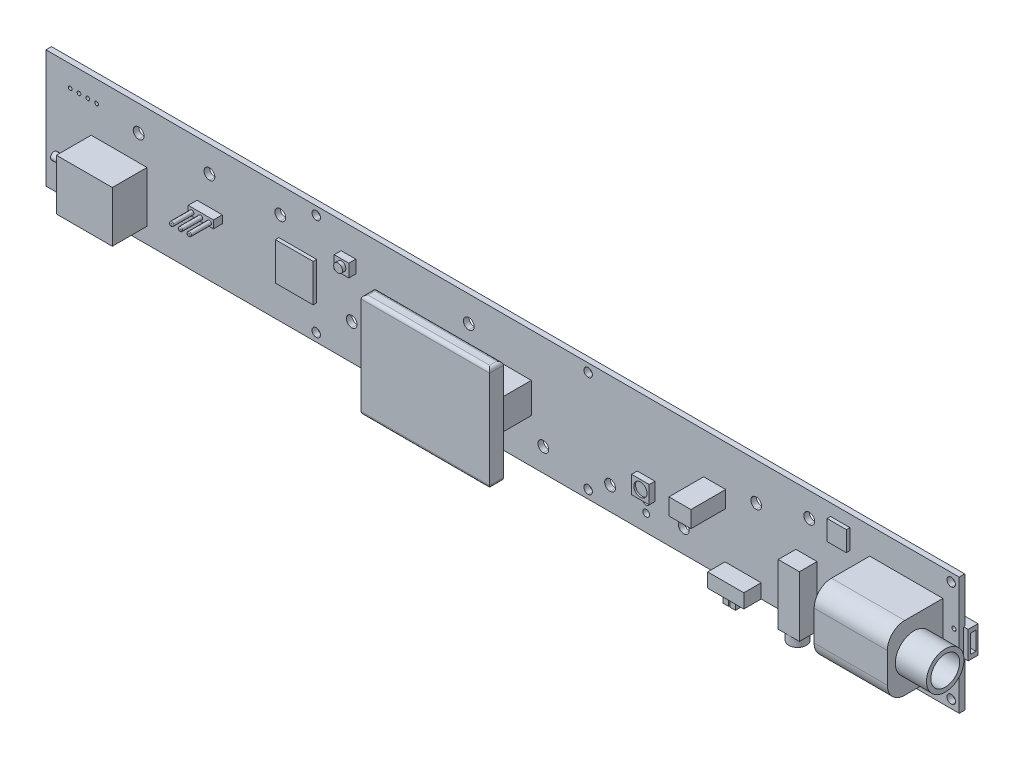
SolidWorks part; units mm, degrees
ref_plane "Front Plane" through (0, 0, 0) normal (0, 0, 1) x (1, 0, 0)
ref_plane "Top Plane" through (0, 0, 0) normal (0, 1, 0) x (1, 0, 0)
ref_plane "Right Plane" through (0, 0, 0) normal (1, 0, 0) x (0, 0, -1)
sketch "Model" plane through (0, 0, 0) normal (0, 0, 1) x (1, 0, 0)
  line L0 (34.6044, 5.9762) -> (297.6294, 5.9762)
  line L1 (297.6294, 5.9762) -> (297.6294, 39.9762)
  line L2 (297.6294, 39.9762) -> (34.6044, 39.9762)
  line L3 (34.6044, 39.9762) -> (34.6044, 5.9762)
  spline S24 degree 3 poles (262.1971, 34.516) (262.0217, 34.516) (261.8796, 34.6582) (261.8796, 34.8335) (261.8796, 35.0089) (262.0217, 35.151) (262.1971, 35.151) knots 2 2 2 2 3 3 3 4 4 4 4
  spline S25 degree 3 poles (262.1971, 35.151) (262.3725, 35.151) (262.5146, 35.0089) (262.5146, 34.8335) (262.5146, 34.6582) (262.3725, 34.516) (262.1971, 34.516) knots 0 0 0 0 1 1 1 2 2 2 2
  spline S48 degree 3 poles (264.4116, 33.4087) (264.2363, 33.4087) (264.0941, 33.5509) (264.0941, 33.7262) (264.0941, 33.9016) (264.2363, 34.0437) (264.4116, 34.0437) knots 2 2 2 2 3 3 3 4 4 4 4
  spline S49 degree 3 poles (264.4116, 34.0437) (264.587, 34.0437) (264.7291, 33.9016) (264.7291, 33.7262) (264.7291, 33.5509) (264.587, 33.4087) (264.4116, 33.4087) knots 0 0 0 0 1 1 1 2 2 2 2
  spline S60 degree 3 poles (295.3194, 36.3663) (294.6456, 36.3663) (294.0994, 36.9125) (294.0994, 37.5863) (294.0994, 38.26) (294.6456, 38.8062) (295.3194, 38.8062) knots 2 2 2 2 3 3 3 4 4 4 4
  spline S61 degree 3 poles (295.3194, 38.8062) (295.9931, 38.8062) (296.5394, 38.26) (296.5394, 37.5863) (296.5394, 36.9125) (295.9931, 36.3663) (295.3194, 36.3663) knots 0 0 0 0 1 1 1 2 2 2 2
  spline S100 degree 3 poles (264.4116, 32.3015) (264.2363, 32.3015) (264.0941, 32.4436) (264.0941, 32.619) (264.0941, 32.7943) (264.2363, 32.9365) (264.4116, 32.9365) knots 2 2 2 2 3 3 3 4 4 4 4
  spline S101 degree 3 poles (264.4116, 32.9365) (264.587, 32.9365) (264.7291, 32.7943) (264.7291, 32.619) (264.7291, 32.4436) (264.587, 32.3015) (264.4116, 32.3015) knots 0 0 0 0 1 1 1 2 2 2 2
  spline S118 degree 3 poles (262.1971, 33.4087) (262.0217, 33.4087) (261.8796, 33.5509) (261.8796, 33.7262) (261.8796, 33.9016) (262.0217, 34.0437) (262.1971, 34.0437) knots 2 2 2 2 3 3 3 4 4 4 4
  spline S119 degree 3 poles (262.1971, 34.0437) (262.3725, 34.0437) (262.5146, 33.9016) (262.5146, 33.7262) (262.5146, 33.5509) (262.3725, 33.4087) (262.1971, 33.4087) knots 0 0 0 0 1 1 1 2 2 2 2
  spline S128 degree 3 poles (112.4394, 36.3763) (111.7656, 36.3763) (111.2194, 36.9225) (111.2194, 37.5962) (111.2194, 38.27) (111.7656, 38.8162) (112.4394, 38.8162) knots 2 2 2 2 3 3 3 4 4 4 4
  spline S129 degree 3 poles (112.4394, 38.8162) (113.1132, 38.8162) (113.6594, 38.27) (113.6594, 37.5962) (113.6594, 36.9225) (113.1132, 36.3763) (112.4394, 36.3763) knots 0 0 0 0 1 1 1 2 2 2 2
  spline S146 degree 3 poles (190.7594, 7.1563) (190.0856, 7.1563) (189.5394, 7.7025) (189.5394, 8.3763) (189.5394, 9.05) (190.0856, 9.5962) (190.7594, 9.5962) knots 2 2 2 2 3 3 3 4 4 4 4
  spline S147 degree 3 poles (190.7594, 9.5962) (191.4331, 9.5962) (191.9794, 9.05) (191.9794, 8.3763) (191.9794, 7.7025) (191.4331, 7.1563) (190.7594, 7.1563) knots 0 0 0 0 1 1 1 2 2 2 2
  spline S150 degree 3 poles (190.7594, 36.3663) (190.0856, 36.3663) (189.5394, 36.9125) (189.5394, 37.5863) (189.5394, 38.26) (190.0856, 38.8062) (190.7594, 38.8062) knots 2 2 2 2 3 3 3 4 4 4 4
  spline S151 degree 3 poles (190.7594, 38.8062) (191.4331, 38.8062) (191.9794, 38.26) (191.9794, 37.5863) (191.9794, 36.9125) (191.4331, 36.3663) (190.7594, 36.3663) knots 0 0 0 0 1 1 1 2 2 2 2
  spline S154 degree 3 poles (263.3044, 33.4087) (263.129, 33.4087) (262.9869, 33.5509) (262.9869, 33.7262) (262.9869, 33.9016) (263.129, 34.0437) (263.3044, 34.0437) knots 2 2 2 2 3 3 3 4 4 4 4
  spline S155 degree 3 poles (263.3044, 34.0437) (263.4797, 34.0437) (263.6219, 33.9016) (263.6219, 33.7262) (263.6219, 33.5509) (263.4797, 33.4087) (263.3044, 33.4087) knots 0 0 0 0 1 1 1 2 2 2 2
  spline S156 degree 3 poles (263.3044, 34.516) (263.129, 34.516) (262.9869, 34.6582) (262.9869, 34.8335) (262.9869, 35.0089) (263.129, 35.151) (263.3044, 35.151) knots 2 2 2 2 3 3 3 4 4 4 4
  spline S157 degree 3 poles (263.3044, 35.151) (263.4797, 35.151) (263.6219, 35.0089) (263.6219, 34.8335) (263.6219, 34.6582) (263.4797, 34.516) (263.3044, 34.516) knots 0 0 0 0 1 1 1 2 2 2 2
  spline S220 degree 3 poles (262.1971, 32.3015) (262.0217, 32.3015) (261.8796, 32.4436) (261.8796, 32.619) (261.8796, 32.7943) (262.0217, 32.9365) (262.1971, 32.9365) knots 2 2 2 2 3 3 3 4 4 4 4
  spline S221 degree 3 poles (262.1971, 32.9365) (262.3725, 32.9365) (262.5146, 32.7943) (262.5146, 32.619) (262.5146, 32.4436) (262.3725, 32.3015) (262.1971, 32.3015) knots 0 0 0 0 1 1 1 2 2 2 2
  spline S222 degree 3 poles (263.3044, 32.3015) (263.129, 32.3015) (262.9869, 32.4436) (262.9869, 32.619) (262.9869, 32.7943) (263.129, 32.9365) (263.3044, 32.9365) knots 2 2 2 2 3 3 3 4 4 4 4
  spline S223 degree 3 poles (263.3044, 32.9365) (263.4797, 32.9365) (263.6219, 32.7943) (263.6219, 32.619) (263.6219, 32.4436) (263.4797, 32.3015) (263.3044, 32.3015) knots 0 0 0 0 1 1 1 2 2 2 2
  spline S228 degree 3 poles (264.4116, 34.516) (264.2363, 34.516) (264.0941, 34.6582) (264.0941, 34.8335) (264.0941, 35.0089) (264.2363, 35.151) (264.4116, 35.151) knots 2 2 2 2 3 3 3 4 4 4 4
  spline S229 degree 3 poles (264.4116, 35.151) (264.587, 35.151) (264.7291, 35.0089) (264.7291, 34.8335) (264.7291, 34.6582) (264.587, 34.516) (264.4116, 34.516) knots 0 0 0 0 1 1 1 2 2 2 2
  spline S252 degree 3 poles (295.3194, 7.1563) (294.6456, 7.1563) (294.0994, 7.7025) (294.0994, 8.3763) (294.0994, 9.05) (294.6456, 9.5962) (295.3194, 9.5962) knots 2 2 2 2 3 3 3 4 4 4 4
  spline S253 degree 3 poles (295.3194, 9.5962) (295.9931, 9.5962) (296.5394, 9.05) (296.5394, 8.3763) (296.5394, 7.7025) (295.9931, 7.1563) (295.3194, 7.1563) knots 0 0 0 0 1 1 1 2 2 2 2
  spline S286 degree 3 poles (112.4394, 7.1563) (111.7656, 7.1563) (111.2194, 7.7025) (111.2194, 8.3763) (111.2194, 9.05) (111.7656, 9.5962) (112.4394, 9.5962) knots 2 2 2 2 3 3 3 4 4 4 4
  spline S287 degree 3 poles (112.4394, 9.5962) (113.1132, 9.5962) (113.6594, 9.05) (113.6594, 8.3763) (113.6594, 7.7025) (113.1132, 7.1563) (112.4394, 7.1563) knots 0 0 0 0 1 1 1 2 2 2 2
  spline S300 degree 3 poles (197.0694, 11.0863) (196.2133, 11.0863) (195.5194, 11.7802) (195.5194, 12.6363) (195.5194, 13.4923) (196.2133, 14.1862) (197.0694, 14.1862) knots 2 2 2 2 3 3 3 4 4 4 4
  spline S301 degree 3 poles (197.0694, 14.1862) (197.9254, 14.1862) (198.6194, 13.4923) (198.6194, 12.6363) (198.6194, 11.7802) (197.9254, 11.0863) (197.0694, 11.0863) knots 0 0 0 0 1 1 1 2 2 2 2
  spline S306 degree 3 poles (122.6494, 14.6662) (121.7933, 14.6662) (121.0994, 15.3602) (121.0994, 16.2162) (121.0994, 17.0723) (121.7933, 17.7662) (122.6494, 17.7662) knots 2 2 2 2 3 3 3 4 4 4 4
  spline S307 degree 3 poles (122.6494, 17.7662) (123.5054, 17.7662) (124.1994, 17.0723) (124.1994, 16.2162) (124.1994, 15.3602) (123.5054, 14.6662) (122.6494, 14.6662) knots 0 0 0 0 1 1 1 2 2 2 2
  spline S312 degree 3 poles (81.6794, 30.9962) (80.8233, 30.9962) (80.1294, 31.6902) (80.1294, 32.5462) (80.1294, 33.4023) (80.8233, 34.0962) (81.6794, 34.0962) knots 2 2 2 2 3 3 3 4 4 4 4
  spline S313 degree 3 poles (81.6794, 34.0962) (82.5354, 34.0962) (83.2294, 33.4023) (83.2294, 32.5462) (83.2294, 31.6902) (82.5354, 30.9962) (81.6794, 30.9962) knots 0 0 0 0 1 1 1 2 2 2 2
  spline S314 degree 3 poles (156.3794, 30.9962) (155.5233, 30.9962) (154.8294, 31.6902) (154.8294, 32.5462) (154.8294, 33.4023) (155.5233, 34.0962) (156.3794, 34.0962) knots 2 2 2 2 3 3 3 4 4 4 4
  spline S315 degree 3 poles (156.3794, 34.0962) (157.2354, 34.0962) (157.9294, 33.4023) (157.9294, 32.5462) (157.9294, 31.6902) (157.2354, 30.9962) (156.3794, 30.9962) knots 0 0 0 0 1 1 1 2 2 2 2
  spline S316 degree 3 poles (254.4194, 31.4562) (253.5633, 31.4562) (252.8694, 32.1502) (252.8694, 33.0062) (252.8694, 33.8623) (253.5633, 34.5562) (254.4194, 34.5562) knots 2 2 2 2 3 3 3 4 4 4 4
  spline S317 degree 3 poles (254.4194, 34.5562) (255.2754, 34.5562) (255.9694, 33.8623) (255.9694, 33.0062) (255.9694, 32.1502) (255.2754, 31.4562) (254.4194, 31.4562) knots 0 0 0 0 1 1 1 2 2 2 2
  spline S318 degree 3 poles (137.8394, 11.0863) (136.9833, 11.0863) (136.2894, 11.7802) (136.2894, 12.6363) (136.2894, 13.4923) (136.9833, 14.1862) (137.8394, 14.1862) knots 2 2 2 2 3 3 3 4 4 4 4
  spline S319 degree 3 poles (137.8394, 14.1862) (138.6954, 14.1862) (139.3894, 13.4923) (139.3894, 12.6363) (139.3894, 11.7802) (138.6954, 11.0863) (137.8394, 11.0863) knots 0 0 0 0 1 1 1 2 2 2 2
  spline S320 degree 3 poles (253.6294, 8.814) (253.1876, 8.814) (252.8294, 9.1722) (252.8294, 9.614) (252.8294, 10.0558) (253.1876, 10.414) (253.6294, 10.414) knots 2 2 2 2 3 3 3 4 4 4 4
  spline S321 degree 3 poles (253.6294, 10.414) (254.0712, 10.414) (254.4294, 10.0558) (254.4294, 9.614) (254.4294, 9.1722) (254.0712, 8.814) (253.6294, 8.814) knots 0 0 0 0 1 1 1 2 2 2 2
  spline S322 degree 3 poles (253.6294, 15.814) (253.1876, 15.814) (252.8294, 16.1722) (252.8294, 16.614) (252.8294, 17.0558) (253.1876, 17.414) (253.6294, 17.414) knots 2 2 2 2 3 3 3 4 4 4 4
  spline S323 degree 3 poles (253.6294, 17.414) (254.0712, 17.414) (254.4294, 17.0558) (254.4294, 16.614) (254.4294, 16.1722) (254.0712, 15.814) (253.6294, 15.814) knots 0 0 0 0 1 1 1 2 2 2 2
  spline S324 degree 3 poles (218.2994, 11.0863) (217.4433, 11.0863) (216.7494, 11.7802) (216.7494, 12.6363) (216.7494, 13.4923) (217.4433, 14.1862) (218.2994, 14.1862) knots 2 2 2 2 3 3 3 4 4 4 4
  spline S325 degree 3 poles (218.2994, 14.1862) (219.1554, 14.1862) (219.8494, 13.4923) (219.8494, 12.6363) (219.8494, 11.7802) (219.1554, 11.0863) (218.2994, 11.0863) knots 0 0 0 0 1 1 1 2 2 2 2
  spline S326 degree 3 poles (237.3794, 7.5013) (237.1032, 7.5013) (236.8794, 7.7251) (236.8794, 8.0013) (236.8794, 8.2774) (237.1032, 8.5013) (237.3794, 8.5013) knots 2 2 2 2 3 3 3 4 4 4 4
  spline S327 degree 3 poles (237.3794, 8.5013) (237.6555, 8.5013) (237.8794, 8.2774) (237.8794, 8.0013) (237.8794, 7.7251) (237.6555, 7.5013) (237.3794, 7.5013) knots 0 0 0 0 1 1 1 2 2 2 2
  spline S328 degree 3 poles (235.3794, 7.5013) (235.1032, 7.5013) (234.8794, 7.7251) (234.8794, 8.0013) (234.8794, 8.2774) (235.1032, 8.5013) (235.3794, 8.5013) knots 2 2 2 2 3 3 3 4 4 4 4
  spline S329 degree 3 poles (235.3794, 8.5013) (235.6555, 8.5013) (235.8794, 8.2774) (235.8794, 8.0013) (235.8794, 7.7251) (235.6555, 7.5013) (235.3794, 7.5013) knots 0 0 0 0 1 1 1 2 2 2 2
  spline S330 degree 3 poles (233.3794, 7.5013) (233.1032, 7.5013) (232.8794, 7.7251) (232.8794, 8.0013) (232.8794, 8.2774) (233.1032, 8.5013) (233.3794, 8.5013) knots 2 2 2 2 3 3 3 4 4 4 4
  spline S331 degree 3 poles (233.3794, 8.5013) (233.6555, 8.5013) (233.8794, 8.2774) (233.8794, 8.0013) (233.8794, 7.7251) (233.6555, 7.5013) (233.3794, 7.5013) knots 0 0 0 0 1 1 1 2 2 2 2
  spline S332 degree 3 poles (239.1594, 27.6263) (238.3033, 27.6263) (237.6094, 28.3202) (237.6094, 29.1763) (237.6094, 30.0323) (238.3033, 30.7262) (239.1594, 30.7262) knots 2 2 2 2 3 3 3 4 4 4 4
  spline S333 degree 3 poles (239.1594, 30.7262) (240.0154, 30.7262) (240.7094, 30.0323) (240.7094, 29.1763) (240.7094, 28.3202) (240.0154, 27.6263) (239.1594, 27.6263) knots 0 0 0 0 1 1 1 2 2 2 2
  spline S334 degree 3 poles (177.8394, 11.0863) (176.9833, 11.0863) (176.2894, 11.7802) (176.2894, 12.6363) (176.2894, 13.4923) (176.9833, 14.1862) (177.8394, 14.1862) knots 2 2 2 2 3 3 3 4 4 4 4
  spline S335 degree 3 poles (177.8394, 14.1862) (178.6954, 14.1862) (179.3894, 13.4923) (179.3894, 12.6363) (179.3894, 11.7802) (178.6954, 11.0863) (177.8394, 11.0863) knots 0 0 0 0 1 1 1 2 2 2 2
  spline S336 degree 3 poles (288.9317, 30.1663) (288.3932, 30.1663) (287.9567, 30.6028) (287.9567, 31.1413) (287.9567, 31.6797) (288.3932, 32.1162) (288.9317, 32.1162) knots 2 2 2 2 3 3 3 4 4 4 4
  spline S337 degree 3 poles (288.9317, 32.1162) (289.4702, 32.1162) (289.9067, 31.6797) (289.9067, 31.1413) (289.9067, 30.6028) (289.4702, 30.1663) (288.9317, 30.1663) knots 0 0 0 0 1 1 1 2 2 2 2
  spline S338 degree 3 poles (282.5817, 30.1663) (282.0432, 30.1663) (281.6067, 30.6028) (281.6067, 31.1413) (281.6067, 31.6797) (282.0432, 32.1162) (282.5817, 32.1162) knots 2 2 2 2 3 3 3 4 4 4 4
  spline S339 degree 3 poles (282.5817, 32.1162) (283.1202, 32.1162) (283.5567, 31.6797) (283.5567, 31.1413) (283.5567, 30.6028) (283.1202, 30.1663) (282.5817, 30.1663) knots 0 0 0 0 1 1 1 2 2 2 2
  spline S340 degree 3 poles (276.2317, 30.1663) (275.6932, 30.1663) (275.2567, 30.6028) (275.2567, 31.1413) (275.2567, 31.6797) (275.6932, 32.1162) (276.2317, 32.1162) knots 2 2 2 2 3 3 3 4 4 4 4
  spline S341 degree 3 poles (276.2317, 32.1162) (276.7702, 32.1162) (277.2067, 31.6797) (277.2067, 31.1413) (277.2067, 30.6028) (276.7702, 30.1663) (276.2317, 30.1663) knots 0 0 0 0 1 1 1 2 2 2 2
  spline S342 degree 3 poles (276.2317, 13.9363) (275.6932, 13.9363) (275.2567, 14.3728) (275.2567, 14.9112) (275.2567, 15.4497) (275.6932, 15.8862) (276.2317, 15.8862) knots 2 2 2 2 3 3 3 4 4 4 4
  spline S343 degree 3 poles (276.2317, 15.8862) (276.7702, 15.8862) (277.2067, 15.4497) (277.2067, 14.9112) (277.2067, 14.3728) (276.7702, 13.9363) (276.2317, 13.9363) knots 0 0 0 0 1 1 1 2 2 2 2
  spline S344 degree 3 poles (282.5817, 13.9363) (282.0432, 13.9363) (281.6067, 14.3728) (281.6067, 14.9112) (281.6067, 15.4497) (282.0432, 15.8862) (282.5817, 15.8862) knots 2 2 2 2 3 3 3 4 4 4 4
  spline S345 degree 3 poles (282.5817, 15.8862) (283.1202, 15.8862) (283.5567, 15.4497) (283.5567, 14.9112) (283.5567, 14.3728) (283.1202, 13.9363) (282.5817, 13.9363) knots 0 0 0 0 1 1 1 2 2 2 2
  spline S346 degree 3 poles (288.9317, 13.9363) (288.3932, 13.9363) (287.9567, 14.3728) (287.9567, 14.9112) (287.9567, 15.4497) (288.3932, 15.8862) (288.9317, 15.8862) knots 2 2 2 2 3 3 3 4 4 4 4
  spline S347 degree 3 poles (288.9317, 15.8862) (289.4702, 15.8862) (289.9067, 15.4497) (289.9067, 14.9112) (289.9067, 14.3728) (289.4702, 13.9363) (288.9317, 13.9363) knots 0 0 0 0 1 1 1 2 2 2 2
  spline S348 degree 3 poles (61.2794, 30.9962) (60.4233, 30.9962) (59.7294, 31.6902) (59.7294, 32.5462) (59.7294, 33.4023) (60.4233, 34.0962) (61.2794, 34.0962) knots 2 2 2 2 3 3 3 4 4 4 4
  spline S349 degree 3 poles (61.2794, 34.0962) (62.1354, 34.0962) (62.8294, 33.4023) (62.8294, 32.5462) (62.8294, 31.6902) (62.1354, 30.9962) (61.2794, 30.9962) knots 0 0 0 0 1 1 1 2 2 2 2
  spline S350 degree 3 poles (41.5694, 33.3262) (41.2656, 33.3262) (41.0194, 33.5725) (41.0194, 33.8762) (41.0194, 34.18) (41.2656, 34.4262) (41.5694, 34.4262) knots 2 2 2 2 3 3 3 4 4 4 4
  spline S351 degree 3 poles (41.5694, 34.4262) (41.8731, 34.4262) (42.1194, 34.18) (42.1194, 33.8762) (42.1194, 33.5725) (41.8731, 33.3262) (41.5694, 33.3262) knots 0 0 0 0 1 1 1 2 2 2 2
  spline S352 degree 3 poles (44.1094, 33.3262) (43.8056, 33.3262) (43.5594, 33.5725) (43.5594, 33.8762) (43.5594, 34.18) (43.8056, 34.4262) (44.1094, 34.4262) knots 2 2 2 2 3 3 3 4 4 4 4
  spline S353 degree 3 poles (44.1094, 34.4262) (44.4131, 34.4262) (44.6594, 34.18) (44.6594, 33.8762) (44.6594, 33.5725) (44.4131, 33.3262) (44.1094, 33.3262) knots 0 0 0 0 1 1 1 2 2 2 2
  spline S354 degree 3 poles (46.6494, 33.3262) (46.3456, 33.3262) (46.0994, 33.5725) (46.0994, 33.8762) (46.0994, 34.18) (46.3456, 34.4262) (46.6494, 34.4262) knots 2 2 2 2 3 3 3 4 4 4 4
  spline S355 degree 3 poles (46.6494, 34.4262) (46.9531, 34.4262) (47.1994, 34.18) (47.1994, 33.8762) (47.1994, 33.5725) (46.9531, 33.3262) (46.6494, 33.3262) knots 0 0 0 0 1 1 1 2 2 2 2
  spline S356 degree 3 poles (49.1894, 33.3262) (48.8856, 33.3262) (48.6394, 33.5725) (48.6394, 33.8762) (48.6394, 34.18) (48.8856, 34.4262) (49.1894, 34.4262) knots 2 2 2 2 3 3 3 4 4 4 4
  spline S357 degree 3 poles (49.1894, 34.4262) (49.4931, 34.4262) (49.7394, 34.18) (49.7394, 33.8762) (49.7394, 33.5725) (49.4931, 33.3262) (49.1894, 33.3262) knots 0 0 0 0 1 1 1 2 2 2 2
  spline S362 degree 3 poles (296.1294, 19.1512) (295.798, 19.1512) (295.5294, 19.4199) (295.5294, 19.7512) (295.5294, 20.0826) (295.798, 20.3512) (296.1294, 20.3512) knots 2 2 2 2 3 3 3 4 4 4 4
  spline S363 degree 3 poles (296.1294, 20.3512) (296.4607, 20.3512) (296.7294, 20.0826) (296.7294, 19.7512) (296.7294, 19.4199) (296.4607, 19.1512) (296.1294, 19.1512) knots 0 0 0 0 1 1 1 2 2 2 2
  spline S364 degree 3 poles (296.1294, 25.7512) (295.798, 25.7512) (295.5294, 26.0199) (295.5294, 26.3512) (295.5294, 26.6826) (295.798, 26.9512) (296.1294, 26.9512) knots 2 2 2 2 3 3 3 4 4 4 4
  spline S365 degree 3 poles (296.1294, 26.9512) (296.4607, 26.9512) (296.7294, 26.6826) (296.7294, 26.3512) (296.7294, 26.0199) (296.4607, 25.7512) (296.1294, 25.7512) knots 0 0 0 0 1 1 1 2 2 2 2
  spline S366 degree 3 poles (102.0694, 30.9962) (101.2133, 30.9962) (100.5194, 31.6902) (100.5194, 32.5462) (100.5194, 33.4023) (101.2133, 34.0962) (102.0694, 34.0962) knots 2 2 2 2 3 3 3 4 4 4 4
  spline S367 degree 3 poles (102.0694, 34.0962) (102.9254, 34.0962) (103.6194, 33.4023) (103.6194, 32.5462) (103.6194, 31.6902) (102.9254, 30.9962) (102.0694, 30.9962) knots 0 0 0 0 1 1 1 2 2 2 2
extrude "Boss-Extrude1" add sketch "Model" along normal blind 1.6
sketch "Sketch5" plane through (0, 0, 1.6) normal (0, 0, 1) x (1, 0, 0)
  line L1 (47.6083, 25.1852) -> (63.6994, 25.1852)
  line L2 (47.6083, 25.1852) -> (47.6083, 10.5157)
  line L3 (47.6083, 10.5157) -> (63.6994, 10.5157)
  line L4 (63.6994, 25.1852) -> (63.6994, 10.5157)
extrude "Boss-Extrude5" add sketch "Sketch5" along normal blind 10
sketch "Sketch7" plane through (0, 0, 1.6) normal (0, 0, 1) x (1, 0, 0)
  line L1 (101.6678, 26.6748) -> (112.5604, 26.6748)
  line L2 (101.6678, 26.6748) -> (101.6678, 15.8259)
  line L3 (101.6678, 15.8259) -> (112.5604, 15.8259)
  line L4 (112.5604, 26.6748) -> (112.5604, 15.8259)
extrude "Boss-Extrude7" add sketch "Sketch7" along normal blind 1
sketch "Sketch8" plane through (0, 0, 1.6) normal (0, 0, 1) x (1, 0, 0)
  line L1 (119.6119, 32.3816) -> (123.8222, 32.3816)
  line L2 (119.6119, 32.3816) -> (119.6119, 28.6694)
  line L3 (119.6119, 28.6694) -> (123.8222, 28.6694)
  line L4 (123.8222, 32.3816) -> (123.8222, 28.6694)
extrude "Boss-Reset Button" add sketch "Sketch8" along normal blind 2
sketch "Sketch9" plane through (0, 0, 3.6) normal (0, 0, 1) x (1, 0, 0)
  circle A0 centre (121.7117, 30.6008) radius 1.2605
extrude "Boss-Extrude9" add sketch "Sketch9" along normal blind 1
sketch "Sketch10" plane through (0, 0, 1.6) normal (0, 0, 1) x (1, 0, 0)
  line L1 (224.0257, 28.1889) -> (230.3583, 28.1889)
  line L2 (224.0257, 28.1889) -> (224.0257, 23.4024)
  line L3 (224.0257, 23.4024) -> (230.3583, 23.4024)
  line L4 (230.3583, 28.1889) -> (230.3583, 23.4024)
extrude "Boss-Extrude10" add sketch "Sketch10" along normal blind 10
sketch "Sketch11" plane through (0, 0, 1.6) normal (0, 0, 1) x (1, 0, 0)
  line L0 (34.6044, 5.9762) -> (297.6294, 5.9762) construction
  line L1 (230.1724, 10.0402) -> (240.5864, 10.0402)
  line L2 (230.1724, 10.0402) -> (230.1724, 5.9762)
  line L3 (230.1724, 5.9762) -> (240.5864, 5.9762)
  line L4 (240.5864, 10.0402) -> (240.5864, 5.9762)
  point P6 (235.3794, 10.0402)
  point P7 (235.3794, 8.5013)
  dimension "D1" = 10.414
  dimension "D2" = 4.064
extrude "Boss-Extrude11" add sketch "Sketch11" along normal blind 5
sketch "Sketch12" plane through (0, 5.9762, 0) normal (0, -1, 0) x (-1, 0, 0)
  line L0 (-230.1724, -6.6) -> (-240.5864, -6.6) construction
  line L1 (-237.1574, -5.6) -> (-235.5826, -5.6)
  line L2 (-237.1574, -5.6) -> (-237.1574, -4.33)
  line L3 (-237.1574, -4.33) -> (-235.5826, -4.33)
  line L4 (-235.5826, -5.6) -> (-235.5826, -4.33)
  line L5 (-240.5864, -6.6) -> (-240.5864, -1.6) construction
  line L6 (-235.3794, -6.6) -> (-235.3794, -50006.6) construction
  line L7 (-235.1762, -5.6) -> (-235.1762, -4.33)
  line L8 (-233.6014, -4.33) -> (-235.1762, -4.33)
  line L9 (-233.6014, -5.6) -> (-233.6014, -4.33)
  line L10 (-233.6014, -5.6) -> (-235.1762, -5.6)
  point P10 (-235.3794, -6.6)
  dimension "D1" = 1.27
  dimension "D2" = 1.5748
  dimension "D3" = 1
  dimension "D4" = 3.429
extrude "Boss-on off button" add sketch "Sketch12" along normal blind 2.54
sketch "Sketch13" plane through (0, 0, 1.6) normal (0, 0, 1) x (1, 0, 0)
  line L0 (240.5864, 5.9762) -> (297.6294, 5.9762) construction
  line L1 (250.5814, 23.3752) -> (256.6774, 23.3752)
  line L2 (250.5814, 23.3752) -> (250.5814, 5.9762)
  line L3 (250.5814, 5.9762) -> (256.6774, 5.9762)
  line L4 (256.6774, 23.3752) -> (256.6774, 5.9762)
  point P6 (253.6294, 17.414)
  point P7 (253.6294, 23.3752)
  dimension "D1" = 6.096
  dimension "D2" = 17.399
extrude "Boss-headphone jack1" add sketch "Sketch13" along normal blind 5.08
sketch "Sketch14" plane through (0, 5.9762, 0) normal (0, -1, 0) x (-1, 0, 0)
  line L1 (-250.5814, -6.68) -> (-256.6774, -6.68) construction
  circle A0 centre (-253.6294, -4.14) radius 2.54
  circle A1 centre (-253.6294, -4.14) radius 1.778
  point P5 (-253.6294, -6.68)
  dimension "D1" = 5.08
  dimension "D3" = 3.556
extrude "Boss-headphone jack2" add sketch "Sketch14" along normal blind 2.5
sketch "Sketch15" plane through (0, 0, 1.6) normal (0, 0, 1) x (1, 0, 0)
  line L1 (266.1183, 30.798) -> (260.5804, 30.798)
  line L2 (266.1183, 30.798) -> (266.1183, 36.5678)
  line L3 (266.1183, 36.5678) -> (260.5804, 36.5678)
  line L4 (260.5804, 30.798) -> (260.5804, 36.5678)
extrude "Boss-Extrude15" add sketch "Sketch15" along normal blind 1
sketch "Sketch16" plane through (0, 0, 1.6) normal (0, 0, 1) x (1, 0, 0)
  line L0 (297.6294, 5.9762) -> (297.6294, 39.9762) construction
  line L1 (271.8484, 32.3107) -> (292.9304, 32.3107)
  line L2 (271.8484, 32.3107) -> (271.8484, 13.6417)
  line L3 (271.8484, 13.6417) -> (292.9304, 13.6417)
  line L4 (292.9304, 32.3107) -> (292.9304, 13.6417)
  point P4 (292.9304, 22.9762)
  point P5 (297.6294, 22.9762)
  dimension "D1" = 18.669
  dimension "D2" = 21.082
  dimension "D3" = 4.699
extrude "Boss-Extrude16" add sketch "Sketch16" along normal blind 16
sketch "Sketch17" plane through (292.9304, 0, 0) normal (1, 0, 0) x (0, 0, -1)
  line L1 (-17.6, 13.6417) -> (-17.6, 32.3107) construction
  line L2 (-1.6, 13.6417) -> (-1.6, 32.3107) construction
  circle A0 centre (-9.9185, 22.9762) radius 5.3975
  circle A1 centre (-9.9185, 22.9762) radius 4.1475
  point P3 (-15.316, 22.9762)
  point P5 (-17.6, 22.9762)
  dimension "D1" = 10.795
  dimension "D3" = 1.25
  dimension "D2" = 13.716
extrude "Boss-Extrude17" add sketch "Sketch17" along normal blind 9
sketch "Sketch18" plane through (0, 0, 0) normal (0, 0, -1) x (-1, 0, 0)
  line L0 (-297.6294, 5.9762) -> (-297.6294, 39.9762) construction
  line L1 (-293.0574, 19.0392) -> (-298.8994, 19.0392)
  line L2 (-293.0574, 19.0392) -> (-293.0574, 26.9132)
  line L3 (-293.0574, 26.9132) -> (-298.8994, 26.9132)
  line L4 (-298.8994, 19.0392) -> (-298.8994, 26.9132)
  point P4 (-293.0574, 22.9762)
  point P5 (-297.6294, 22.9762)
  dimension "D1" = 7.874
  dimension "D2" = 5.842
  dimension "D3" = 1.27
extrude "Boss-Extrude18" add sketch "Sketch18" along normal blind 2.54 and the other way blind 0.3
sketch "Sketch19" plane through (298.8994, 0, 0) normal (1, 0, 0) x (0, 0, -1)
  line L0 (-0.3, 26.9132) -> (-0.3, 19.0392) construction
  line L1 (0.3225, 25.6161) -> (1.9175, 25.6161)
  line L2 (0.3225, 25.6161) -> (0.3225, 20.3364)
  line L3 (0.3225, 20.3364) -> (1.9175, 20.3364)
  line L4 (1.9175, 25.6161) -> (1.9175, 20.3364)
  line L5 (-0.3, 19.0392) -> (2.54, 19.0392) construction
  point P4 (-0.3, 22.9762)
  point P5 (1.12, 19.0392)
  point P8 (1.12, 20.3364)
  point P11 (0.3225, 22.9762)
  dimension "D1" = 1.5949
  dimension "D2" = 5.2798
extrude "Cut-Extrude1" cut sketch "Sketch19" against normal blind 5
fillet "Fillet1" radius 5 2 edges at (282.3894, 13.6417, 17.6) (282.3894, 32.3107, 17.6)
sketch "Sketch20" plane through (0, 0, 0) normal (0, 0, -1) x (-1, 0, 0)
  line L1 (-153.3741, 15.6562) -> (-159.3741, 15.6562)
  line L2 (-153.3741, 15.6562) -> (-153.3741, 9.6562)
  line L3 (-153.3741, 9.6562) -> (-159.3741, 9.6562)
  line L4 (-159.3741, 15.6562) -> (-159.3741, 9.6562)
extrude "Boss-Extrude19" add sketch "Sketch20" along normal blind 3
sketch "Sketch21" plane through (0, 0, -3) normal (0, 0, -1) x (-1, 0, 0)
  circle A0 centre (-156.3741, 12.6562) radius 2.5
extrude "Boss-Extrude20" add sketch "Sketch21" along normal blind 11
sketch "Sketch22" plane through (47.6083, 0, 0) normal (-1, 0, 0) x (0, 0, 1)
  circle A0 centre (9.2733, 22.4128) radius 1.0397
extrude "Boss-Extrude21" add sketch "Sketch22" along normal blind 3
sketch "Sketch23" plane through (0, 0, 1.6) normal (0, 0, 1) x (1, 0, 0)
  line L1 (209.9994, 20.0732) -> (204.9194, 20.0732)
  line L2 (209.9994, 20.0732) -> (209.9994, 14.9932)
  line L3 (209.9994, 14.9932) -> (204.9194, 14.9932)
  line L4 (204.9194, 20.0732) -> (204.9194, 14.9932)
  line L5 (297.6294, 5.9762) -> (297.6294, 39.9762) construction
  line L6 (34.6044, 5.9762) -> (230.1724, 5.9762) construction
  point P4 (209.9994, 17.5332)
  point P5 (209.9994, 20.0732)
  dimension "D1" = 5.08
  dimension "D2" = 5.08
  dimension "D3" = 11.557
  dimension "D4" = 87.63
extrude "Boss-Extrude22" add sketch "Sketch23" along normal blind 1.651
sketch "Sketch24" plane through (0, 0, 1.6) normal (0, 0, 1) x (1, 0, 0)
  line L1 (162.3602, 7.0303) -> (164.1142, 7.0303)
  line L2 (150.0172, 7.8131) -> (150.0172, 23.0303)
  line L3 (150.0172, 23.0303) -> (164.1142, 23.0303)
  line L4 (164.1142, 7.0303) -> (164.1142, 23.0303)
  arc A0 (150.0172, 7.8131) -> (162.3602, 7.0303) centre (155.5056, -3.3494) cw
  dimension "D1" = 14.097
extrude "Boss-Extrude23" add sketch "Sketch24" along normal blind 1.905
sketch "Sketch25" plane through (0, 7.0303, 0) normal (0, -1, 0) x (1, 0, 0)
  line L1 (162.0518, 3.312) -> (150.2385, 3.312)
  line L2 (162.0518, 3.312) -> (162.0518, 1.8513)
  line L3 (162.0518, 1.8513) -> (150.2385, 1.8513)
  line L4 (150.2385, 3.312) -> (150.2385, 1.8513)
extrude "Boss-Extrude24" add sketch "Sketch25" along normal blind 1.5 and the other way blind 10
sketch "Sketch26" plane through (0, 0, 3.312) normal (0, 0, 1) x (1, 0, 0)
  line L0 (150.2385, 7.9192) -> (150.2385, 5.5303) construction
  line L1 (162.0518, 5.5303) -> (150.2385, 5.5303)
  line L2 (162.0518, 5.5303) -> (162.0518, 6.0157)
  line L4 (150.2385, 5.5303) -> (150.2385, 6.0157)
  arc A0 (150.2385, 6.0157) -> (162.0518, 6.0157) centre (156.1451, -17.2242) cw
extrude "Boss-Extrude25" add sketch "Sketch26" along normal blind 0.5
sketch "Sketch27" plane through (0, 0, 3.251) normal (0, 0, 1) x (1, 0, 0)
  line L0 (209.9994, 20.0732) -> (204.9194, 14.9932) construction
  circle A0 centre (207.4594, 17.5332) radius 1.905
  point P6 (207.4594, 17.5332)
  dimension "D1" = 3.81
extrude "Cut-Extrude2" cut sketch "Sketch27" against normal blind 0.5
sketch "Sketch28" plane through (0, 0, 1.6) normal (0, 0, 1) x (1, 0, 0)
  line L1 (165.185, 27.4281) -> (174.3843, 27.4281)
  line L2 (165.185, 27.4281) -> (165.185, 18.6324)
  line L3 (165.185, 18.6324) -> (174.3843, 18.6324)
  line L4 (174.3843, 27.4281) -> (174.3843, 18.6324)
extrude "Boss-Extrude26" add sketch "Sketch28" along normal blind 10
sketch "Sketch29" plane through (0, 0, 11.6) normal (0, 0, 1) x (1, 0, 0)
  line L1 (139.3717, 38.1853) -> (176.3717, 38.1853)
  line L2 (139.3717, 38.1853) -> (139.3717, 8.1853)
  line L3 (139.3717, 8.1853) -> (176.3717, 8.1853)
  line L4 (176.3717, 38.1853) -> (176.3717, 8.1853)
extrude "Boss-Extrude27" add sketch "Sketch29" along normal blind 4
fillet "Fillet3" radius 1 8 edges at (176.3717, 38.1853, 13.6) (157.8717, 38.1853, 15.6) (139.3717, 38.1853, 13.6) (157.8717, 38.1853, 11.6) (139.3717, 8.1853, 13.6) (157.8717, 8.1853, 15.6) (176.3717, 8.1853, 13.6) (157.8717, 8.1853, 11.6)
sketch "Sketch30" plane through (0, 0, 0) normal (0, 0, -1) x (-1, 0, 0)
  line L1 (-280.5345, 19.2742) -> (-272.5058, 19.2742)
  line L2 (-280.5345, 19.2742) -> (-280.5345, 27.8954)
  line L3 (-280.5345, 27.8954) -> (-272.5058, 27.8954)
  line L4 (-272.5058, 19.2742) -> (-272.5058, 27.8954)
extrude "Boss-Extrude28" add sketch "Sketch30" along normal blind 5
sketch "Sketch31" plane through (0, 0, -5) normal (0, 0, -1) x (-1, 0, 0)
  line L1 (-291.7697, 11.3403) -> (-261.7697, 11.3403)
  line L2 (-291.7697, 11.3403) -> (-291.7697, 36.3403)
  line L3 (-291.7697, 36.3403) -> (-261.7697, 36.3403)
  line L4 (-261.7697, 11.3403) -> (-261.7697, 36.3403)
sketch "Sketch34" plane through (0, 0, 0) normal (0, 0, -1) x (-1, 0, 0)
  line L0 (-297.6294, 39.9762) -> (-34.6044, 39.9762) construction
  line L1 (-34.6044, 39.9762) -> (-34.6044, 5.9762) construction
  point P0 (-166.1169, 39.9762)
  point P1 (-34.6044, 22.9762)
ref_plane "Plane - Front" through (0, 22.9762, 0) normal (0, 1, 0) x (1, 0, 0)
ref_plane "Plane - Right" through (166.1169, 0, 0) normal (1, 0, 0) x (0, 0, -1)
sketch "Sketch35" plane through (0, 0, 1.6) normal (0, 0, 1) x (1, 0, 0)
  line L1 (34.6044, 5.9762) -> (230.1724, 5.9762) construction
  line L3 (34.6044, 39.9762) -> (34.6044, 5.9762) construction
  circle A0 centre (81.6794, 22.9762) radius 0.6
  circle A1 centre (79.1394, 22.9762) radius 0.6
  circle A2 centre (84.2194, 22.9762) radius 0.6
  dimension "D2" = 47.075
  dimension "D1" = 17
extrude "Boss-Extrude29" add sketch "Sketch35" along normal blind 8.54
sketch "Sketch36" plane through (0, 0, 1.6) normal (0, 0, 1) x (1, 0, 0)
  line L1 (85.3726, 21.9692) -> (78.1102, 21.9692)
  line L2 (85.3726, 21.9692) -> (85.3726, 24.206)
  line L3 (85.3726, 24.206) -> (78.1102, 24.206)
  line L4 (78.1102, 21.9692) -> (78.1102, 24.206)
extrude "Boss-Extrude30" add sketch "Sketch36" along normal blind 2.54
fillet "Fillet5" radius 0.25 3 edges at (79.7394, 22.9762, 10.14) (82.2794, 22.9762, 10.14) (84.8194, 22.9762, 10.14)
sketch "Sketch37" plane through (0, 0, 1.6) normal (0, 0, 1) x (1, 0, 0)
  line L0 (295.3194, 38.8062) -> (295.3194, 36.3663) construction
  line L1 (295.3194, 9.5962) -> (295.3194, 7.1563) construction
  circle A0 centre (295.3194, 37.5863) radius 1.1027
  circle A1 centre (295.3194, 8.3763) radius 1.0693
sketch "Sketch38" plane through (0, 0, 1.6) normal (0, 0, 1) x (1, 0, 0)
  circle A0 centre (207.4594, 13.8232) radius 0.965
  circle A1 centre (207.4594, 10.8532) radius 0.965
  point P4 (207.4594, 17.5332)
  dimension "D1" = 1.93
  dimension "D2" = 2.97
  dimension "D3" = 6.68
extrude "LED pin holes" cut sketch "Sketch38" against normal through all
fillet "Fillet6" radius 0.75 1 edges at (153.8741, 12.6562, -14)
